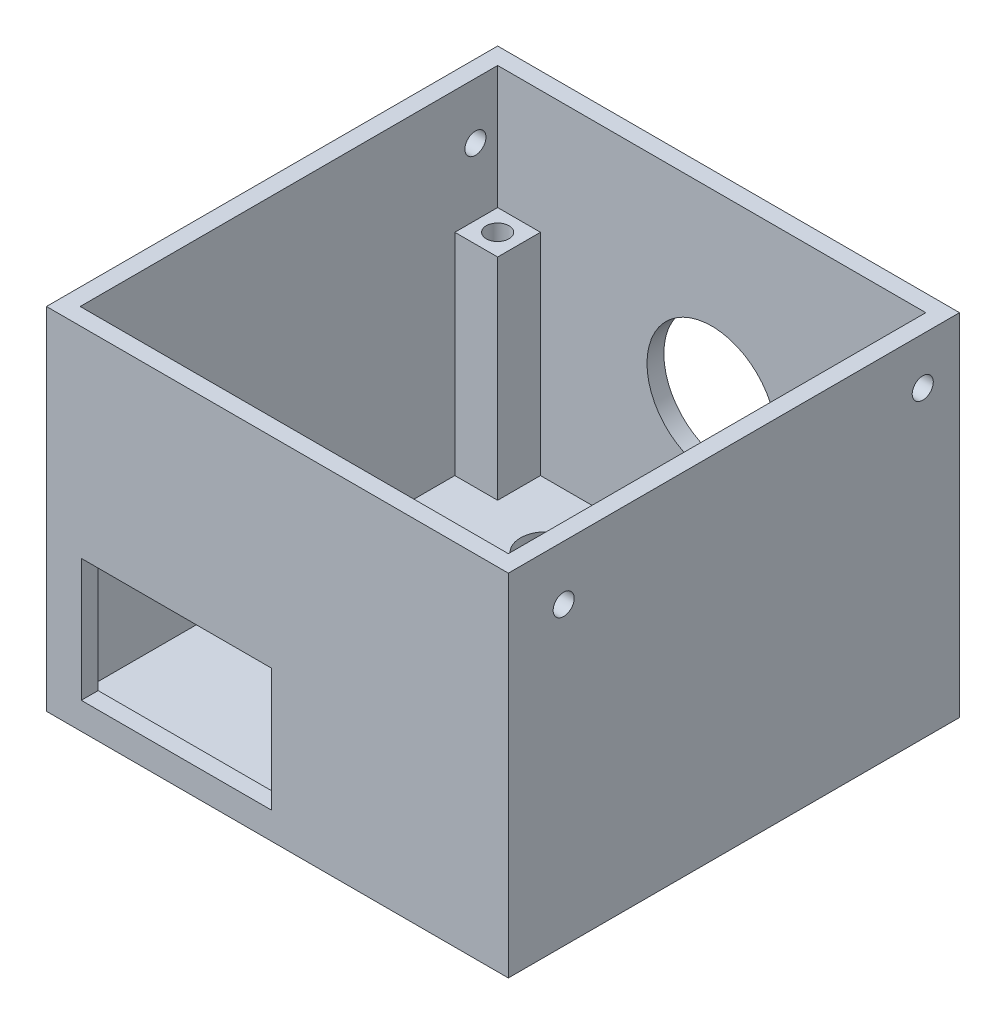
SolidWorks part; units mm, degrees
ref_plane "Front Plane" through (0, 0, 0) normal (0, 0, 1) x (1, 0, 0)
ref_plane "Top Plane" through (0, 0, 0) normal (0, 1, 0) x (1, 0, 0)
ref_plane "Right Plane" through (0, 0, 0) normal (1, 0, 0) x (0, 0, -1)
sketch "Sketch1" plane through (0, 0, 0) normal (0, 1, 0) x (1, 0, 0)
  line L1 (27.4, -26.765) -> (-27.4, -26.765)
  line L2 (27.4, -26.765) -> (27.4, 26.765)
  line L3 (27.4, 26.765) -> (-27.4, 26.765)
  line L4 (-27.4, -26.765) -> (-27.4, 26.765)
  line L5 (27.4, -26.765) -> (-27.4, 26.765) construction
  line L6 (27.4, 26.765) -> (-27.4, -26.765) construction
  point P0 (0, 0)
  dimension "D1" = 54.8
  dimension "D2" = 53.53
extrude "Boss-Extrude1" add sketch "Sketch1" along normal blind 41.6
sketch "Sketch2" plane through (0, 41.6, 0) normal (0, 1, 0) x (1, 0, 0)
  line L0 (-27.4, 26.765) -> (-27.4, -26.765) construction
  line L1 (25.4, -24.765) -> (-25.4, -24.765)
  line L2 (25.4, -24.765) -> (25.4, 24.765)
  line L3 (25.4, 24.765) -> (-25.4, 24.765)
  line L4 (-25.4, -24.765) -> (-25.4, 24.765)
  line L5 (25.4, -24.765) -> (-25.4, 24.765) construction
  line L6 (25.4, 24.765) -> (-25.4, -24.765) construction
  line L7 (27.4, 26.765) -> (-27.4, 26.765) construction
  point P0 (0, 0)
  dimension "D1" = 2
  dimension "D2" = 2
extrude "Cut-Extrude1" cut sketch "Sketch2" against normal blind 39.6
sketch "Sketch3" plane through (0, 2, 0) normal (0, 1, 0) x (1, 0, 0)
  line L1 (-25.4, 24.765) -> (-20.32, 24.765)
  line L2 (-25.4, 24.765) -> (-25.4, 19.685)
  line L3 (-25.4, 19.685) -> (-20.32, 19.685)
  line L4 (-20.32, 24.765) -> (-20.32, 19.685)
  line L5 (25.4, 24.765) -> (20.32, 24.765)
  line L6 (25.4, 24.765) -> (25.4, 19.685)
  line L7 (25.4, 19.685) -> (20.32, 19.685)
  line L8 (20.32, 24.765) -> (20.32, 19.685)
  line L9 (25.4, -24.765) -> (20.32, -24.765)
  line L10 (25.4, -24.765) -> (25.4, -19.685)
  line L11 (25.4, -19.685) -> (20.32, -19.685)
  line L12 (20.32, -24.765) -> (20.32, -19.685)
  dimension "D1" = 5.08
  dimension "D2" = 5.08
  dimension "D3" = 5.08
  dimension "D4" = 5.08
  dimension "D5" = 5.08
  dimension "D6" = 5.08
extrude "Boss-Extrude2" add sketch "Sketch3" along normal blind 25
sketch "Sketch4" plane through (0, 27, 0) normal (0, 1, 0) x (1, 0, 0)
  line L0 (-20.32, 19.685) -> (-20.32, 24.765) construction
  line L3 (-25.4, 19.685) -> (-20.32, 19.685) construction
  line L4 (20.32, 19.685) -> (25.4, 19.685) construction
  line L5 (20.32, 24.765) -> (20.32, 19.685) construction
  line L6 (25.4, -19.685) -> (20.32, -19.685) construction
  line L7 (20.32, -19.685) -> (20.32, -24.765) construction
  circle A0 centre (-22.86, 22.225) radius 1.35
  circle A1 centre (22.86, 22.225) radius 1.35
  circle A2 centre (22.86, -22.225) radius 1.35
  point P12 (22.86, -19.685)
  dimension "D1" = 2.54
  dimension "D3" = 2.54
  dimension "D5" = 2.54
  dimension "D2" = 2.54
  dimension "D4" = 2.54
  dimension "D6" = 2.54
extrude "Cut-Extrude2" cut sketch "Sketch4" against normal blind 10
sketch "Sketch5" plane through (0, 0, 0) normal (0, -1, 0) x (-1, 0, 0)
  circle A0 centre (-12.7629, 17.1869) radius 3
  circle A1 centre (12.1084, 17.1869) radius 3
extrude "Cut-Extrude3" cut sketch "Sketch5" against normal up to next
sketch "Sketch6" plane through (0, 0, 0) normal (0, -1, 0) x (-1, 0, 0)
  circle A0 centre (-16.7643, 3.6231) radius 2
  circle A1 centre (-16.7643, -2.0736) radius 2
extrude "Cut-Extrude4" cut sketch "Sketch6" against normal up to next
sketch "Sketch7" plane through (0, 0, 0) normal (0, -1, 0) x (-1, 0, 0)
  circle A0 centre (-16.6778, -12.0076) radius 2
extrude "Cut-Extrude5" cut sketch "Sketch7" against normal up to next
sketch "Sketch8" plane through (27.4, 0, 0) normal (1, 0, 0) x (0, 0, -1)
  circle A0 centre (-20.2009, 35.1133) radius 1.25
extrude "Cut-Extrude6" cut sketch "Sketch8" against normal up to next
sketch "Sketch10" plane through (-27.4, 0, 0) normal (-1, 0, 0) x (0, 0, 1)
  circle A0 centre (-22.1268, 34.9354) radius 1.25
extrude "Cut-Extrude7" cut sketch "Sketch10" against normal up to next
sketch "Sketch12" plane through (0, 0, -26.765) normal (0, 0, -1) x (-1, 0, 0)
  circle A0 centre (0, 19.8508) radius 7.6805
extrude "Cut-Extrude8" cut sketch "Sketch12" against normal up to next
sketch "Sketch13" plane through (0, 0, 26.765) normal (0, 0, 1) x (1, 0, 0)
  line L1 (-0.6897, 3.1964) -> (-23.2715, 3.1964)
  line L2 (-0.6897, 3.1964) -> (-0.6897, 17.7861)
  line L3 (-0.6897, 17.7861) -> (-23.2715, 17.7861)
  line L4 (-23.2715, 3.1964) -> (-23.2715, 17.7861)
  line L5 (-0.6897, 3.1964) -> (-23.2715, 17.7861) construction
  line L6 (-0.6897, 17.7861) -> (-23.2715, 3.1964) construction
  point P0 (-11.9806, 10.4912)
extrude "Cut-Extrude9" cut sketch "Sketch13" against normal up to next
sketch "Sketch14" plane through (27.4, 0, 0) normal (1, 0, 0) x (0, 0, -1)
  circle A0 centre (22.4032, 36.0407) radius 1.25
extrude "Cut-Extrude10" cut sketch "Sketch14" against normal up to next
